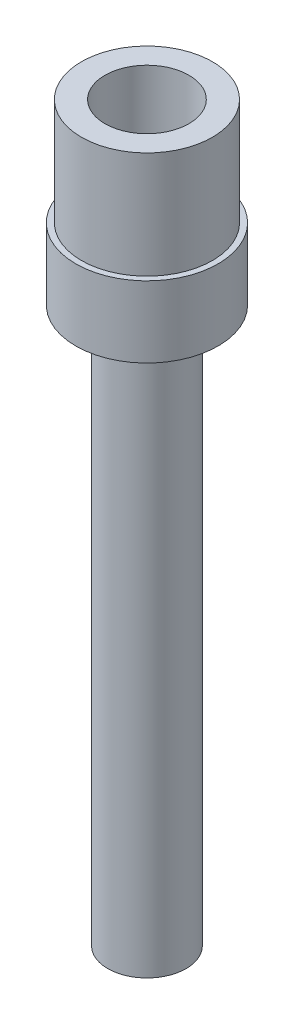
SolidWorks part; units mm, degrees
material "1023 Carbon Steel Sheet (SS)"
ref_plane "Front Plane" through (0, 0, 0) normal (0, 0, 1) x (1, 0, 0)
ref_plane "Top Plane" through (0, 0, 0) normal (0, 1, 0) x (1, 0, 0)
ref_plane "Right Plane" through (0, 0, 0) normal (1, 0, 0) x (0, 0, -1)
sketch "Sketch1" plane through (0, 0, 0) normal (0, 1, 0) x (1, 0, 0)
  circle A0 centre (0, 0) radius 2.58
  circle A1 centre (0, 0) radius 5.5
  circle A2 centre (0, 0) radius 4.58 construction
  dimension "D1" = 2
  dimension "D2" = 11
  dimension "D3" = 5.16
  dimension "D4" = 9.16
extrude "Boss-Extrude1" add sketch "Sketch1" along normal blind 78
sketch "Sketch2" plane through (0, 0, 0) normal (0, -1, 0) x (1, 0, 0)
  circle A0 centre (0, 0) radius 5.5
  circle A1 centre (0, 0) radius 5.5 construction
  circle A2 centre (0, 0) radius 5.5
  dimension "D1" = 11
sketch "Sketch4" plane through (0, 78, 0) normal (0, 1, 0) x (1, 0, 0)
  circle A0 centre (0, 0) radius 3.4
  circle A2 centre (0, 0) radius 5.5 construction
  circle M3 centre (0, 0) radius 2.58
  dimension "D1" = 6.8
  dimension "D2" = 2.1
extrude "Cut-Extrude2" cut sketch "Sketch4" against normal blind 65 contours A0 M3 region at (-3.3038, 78, 0)
sketch "Sketch5" plane through (0, 78, 0) normal (0, 1, 0) x (1, 0, 0)
  circle A0 centre (0, 0) radius 10
  point P2 (1.103, 0.5664)
  point P3 (0, 0)
  circle M2 centre (0, 0) radius 3.4
  circle M3 centre (0, 0) radius 5.5
  dimension "D1" = 20
extrude "Boss-Extrude2" add sketch "Sketch5" along normal blind 10 contours M3 M2 | A0 M3 region at (-9.7172, 78, 0) region at (-5.3444, 78, 0)
chamfer "Chamfer1" distance 2.5 angle 45 1 edges at (0, 88, 3.4)
sketch "Sketch6" plane through (0, 88, 0) normal (0, 1, 0) x (1, 0, 0)
  circle A0 centre (0, 0) radius 9.2
  circle A3 centre (0, 0) radius 10 construction
  circle M2 centre (0, 0) radius 5.9
  dimension "D1" = 0.8
extrude "Boss-Extrude3" add sketch "Sketch6" along normal blind 15 contours M2 | A0 M2 region at (-8.9398, 88, 0) region at (0, 88, 0)
hole_wizard "G1/4 Tapped Hole2" positions "Sketch10" profile "Sketch11" tap size "G1/4" standard "ISO"
sketch "Sketch10" plane through (0, 103, 0) normal (0, 1, 0) x (1, 0, 0)
  point P0 (0, 0)
sketch "Sketch11" plane through (0, 103, 0) normal (1, 0, 0) x (0, 0, 1)
  line L0 (0, 0) -> (0, 18.5451)
  line L1 (0, 18.5451) -> (5.9, 15)
  line L2 (5.9, 15) -> (5.9, 0)
  line L5 (5.9, 0) -> (0, 0)
  line L10 (0, 18.5451) -> (-5.9, 15) construction
  line L11 (0, -6.35) -> (0, 107.95) construction
  dimension "Tap Drill Dia." = 11.8
  dimension "Tap Drill Depth" = 15
  dimension "Drill Angle" = 118
cosmetic thread "Hole Thread1" parameters "D1"=26.314, "D2"=13.157
chamfer "Chamfer2" distance 0.45 angle 62 1 edges at (0, 13, 2.58) first distance on face at (0, 0, 2.58)
